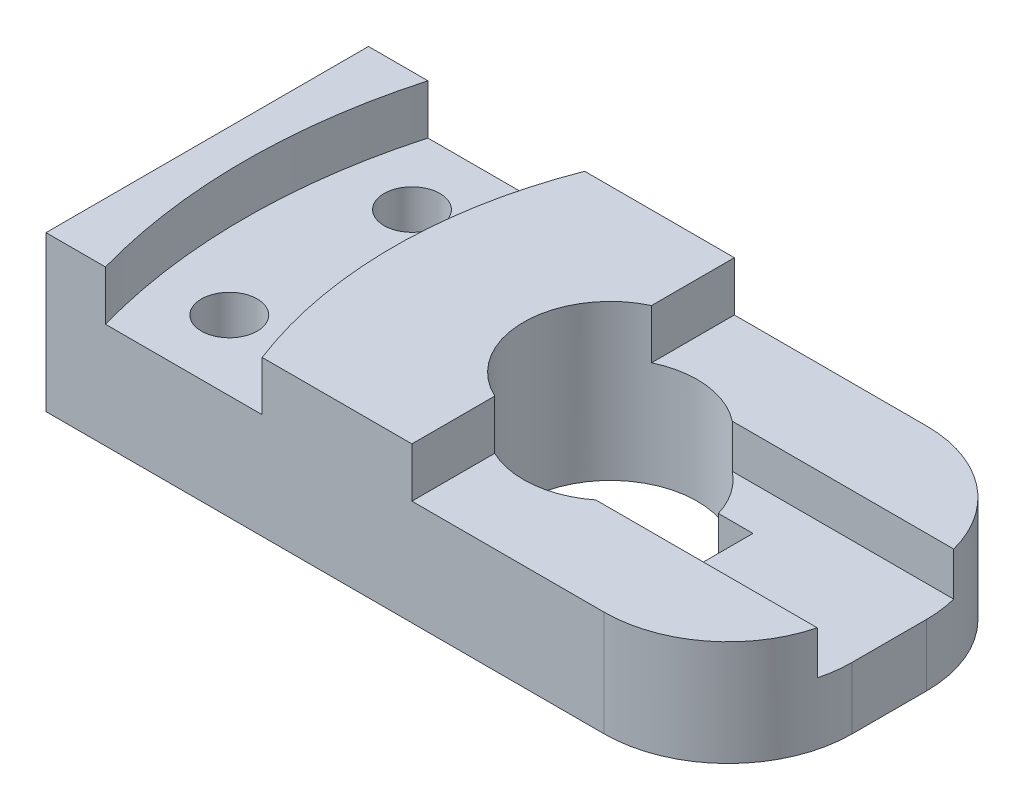
SolidWorks part; units mm, degrees
ref_plane "Front Plane" through (0, 0, 0) normal (0, 0, 1) x (1, 0, 0)
ref_plane "Top Plane" through (0, 0, 0) normal (0, 1, 0) x (1, 0, 0)
ref_plane "Right Plane" through (0, 0, 0) normal (1, 0, 0) x (0, 0, -1)
sketch "Sketch1" plane through (0, 0, 0) normal (0, 1, 0) x (1, 0, 0)
  line L0 (0, 0) -> (51, 0) construction
  line L1 (0, -26) -> (90, -26)
  line L2 (0, -26) -> (0, 26)
  line L3 (0, 26) -> (90, 26)
  line L4 (110, -6) -> (110, 6)
  line L5 (65, 0) -> (9.1885, 17.5973) construction
  line L6 (84, -4) -> (84, 4)
  line L7 (84, 4) -> (78.4164, 4)
  line L8 (84, -4) -> (78.4164, -4)
  line L9 (84, 0) -> (155.1175, 0) construction
  line L10 (59, -12.6491) -> (59, -26)
  line L11 (110, 6) -> (77.6491, 6)
  line L12 (73.6603, 11) -> (109.3649, 11)
  line L13 (59, 12.6491) -> (59, 26)
  line L14 (65, 0) -> (9.1885, -17.5973) construction
  line L15 (73.6603, -11) -> (109.3649, -11)
  arc A0 (110, 6) -> (90, 26) centre (90, 6) ccw
  arc A1 (90, -26) -> (110, -6) centre (90, -6) ccw
  arc A2 (78.4164, 4) -> (78.4164, -4) centre (65, 0) ccw
  arc A3 (9.5879, 26) -> (9.5879, -26) centre (102, 0) ccw
  arc A4 (21.0741, 26) -> (21.0741, -26) centre (102, 0) ccw construction
  circle A5 centre (18.2858, 14.7289) radius 4.5
  arc A6 (34.8584, 26) -> (34.8584, -26) centre (102, 0) ccw
  circle A7 centre (18.2858, -14.7289) radius 4.5
  arc A8 (110, -6) -> (90, -26) centre (90, -6) cw
  point P4 (0, 0)
  point P12 (110, 0)
  point P14 (102, 0)
  point P19 (84, 0)
  point P24 (18.2858, 14.7289)
  dimension "D2" = 28
  dimension "D10" = 96
  dimension "D11" = 9
  dimension "D12" = 85
  dimension "D13" = 72
  dimension "D15" = 20
  dimension "D3" = 110
  dimension "D4" = 52
  dimension "D5" = 19
  dimension "D6" = 8
  dimension "D7" = 45
  dimension "D8" = 8
  dimension "D9" = 17.5
  dimension "D14" = 51
  dimension "D16" = 22
extrude "Boss-Extrude1" add sketch "Sketch1" along normal blind 25 contours A3 L3 L2 L1 region at (3.6726, 0, 0)
extrude "Boss-Extrude2" add sketch "Sketch1<3>" along normal blind 17 contours A6 L3 A3 L1 A5 A7 | A2 L12 A0 L3 L13 | A2 L10 L1 A1 L15 | L3 A6 L1 L10 A2 L13 region at (19.5365, 0, 0) region at (44.0757, 0, 0) region at (82.7226, 0, 18.4026) region at (82.7226, 0, -18.4026)
sketch "Sketch1<3>" plane through (0, 0, 0) normal (0, 1, 0) x (1, 0, 0) same geometry as "Sketch1"
extrude "Boss-Extrude3" add sketch "Sketch1<4>" along normal blind 25 contours L3 A6 L1 L10 A2 L13 region at (44.0757, 0, 0)
sketch "Sketch1<4>" plane through (0, 0, 0) normal (0, 1, 0) x (1, 0, 0) same geometry as "Sketch1"
extrude "Boss-Extrude4" add sketch "Sketch1<5>" along normal blind 10 contours A2 L11 A0 L12 | A2 L15 A1 L4 L11 L7 L6 L8 region at (94.8624, 0, 2.8605) region at (92.8618, 0, -8.5405)
sketch "Sketch1<5>" plane through (0, 0, 0) normal (0, 1, 0) x (1, 0, 0) same geometry as "Sketch1"
